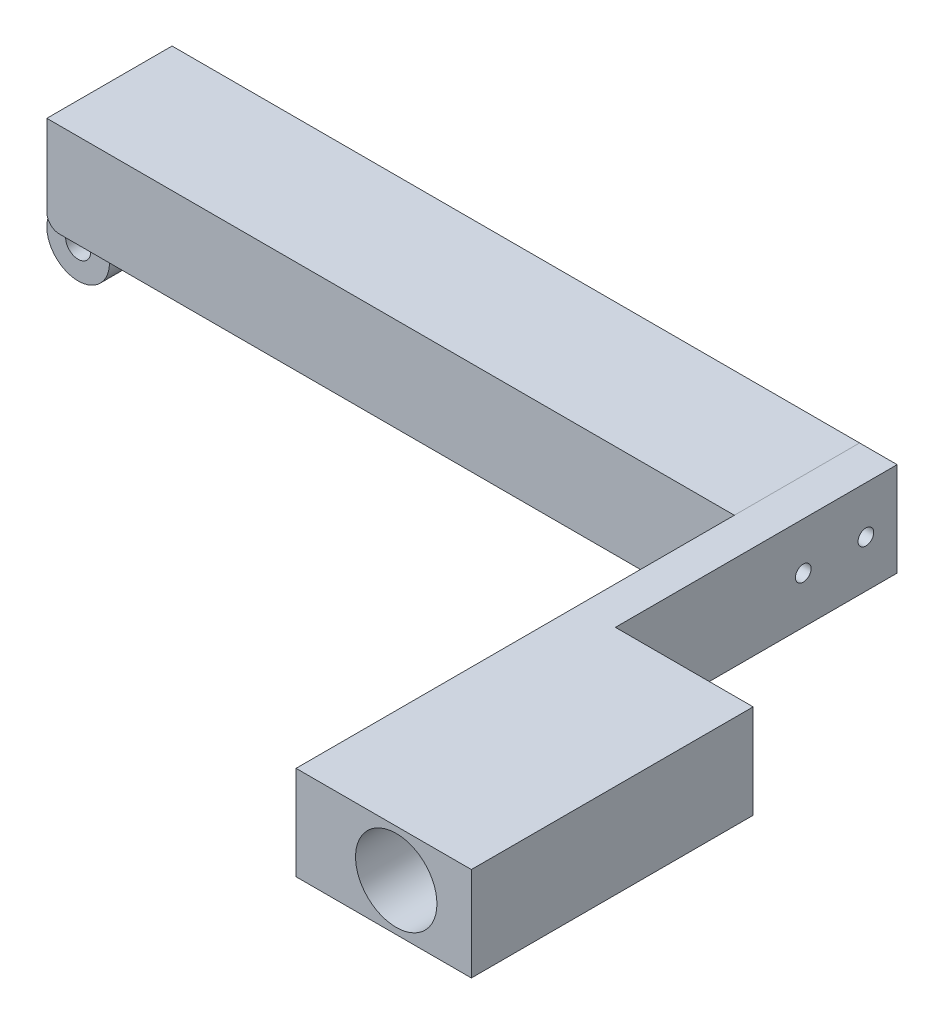
SolidWorks part; units mm, degrees
ref_plane "Front Plane" through (0, 0, 0) normal (0, 0, 1) x (1, 0, 0)
ref_plane "Top Plane" through (0, 0, 0) normal (0, 1, 0) x (1, 0, 0)
ref_plane "Right Plane" through (0, 0, 0) normal (1, 0, 0) x (0, 0, -1)
sketch "Sketch4" plane through (0, 0, 0) normal (1, 0, 0) x (0, 0, -1)
  line L1 (-10, -7.5) -> (10, -7.5)
  line L2 (-10, -7.5) -> (-10, 7.5)
  line L3 (-10, 7.5) -> (10, 7.5)
  line L4 (10, -7.5) -> (10, 7.5)
  line L5 (-10, -7.5) -> (10, 7.5) construction
  line L6 (-10, 7.5) -> (10, -7.5) construction
  point P0 (0, 0)
  dimension "D1" = 20
  dimension "D2" = 15
extrude "Boss-Extrude1" add sketch "Sketch4" along normal blind 115.8
sketch "Sketch5" plane through (0, 0, 10) normal (0, 0, 1) x (1, 0, 0)
  line L0 (115.8, -7.5) -> (0, -7.5) construction
  line L1 (115.8, 7.5) -> (109.8, 7.5)
  line L2 (115.8, 7.5) -> (115.8, -7.5)
  line L3 (115.8, -7.5) -> (109.8, -7.5)
  line L4 (109.8, 7.5) -> (109.8, -7.5)
  dimension "D1" = 6
extrude "Boss-Extrude2" add sketch "Sketch5" along normal blind 35
sketch "Sketch6" plane through (0, 0, 45) normal (0, 0, 1) x (1, 0, 0)
  line L0 (115.8, -7.5) -> (115.8, 7.5) construction
  line L2 (109.8, -7.5) -> (137.8, -7.5)
  line L3 (109.8, -7.5) -> (109.8, 7.5)
  line L4 (109.8, 7.5) -> (137.8, 7.5)
  line L5 (137.8, -7.5) -> (137.8, 7.5)
  line L6 (123.8, 7.5) -> (123.8, -7.5) construction
  line L7 (109.8, 0) -> (137.8, 0) construction
  circle A0 centre (125.8, 0) radius 6.5
  point P6 (115.8, 0)
  point P213 (123.8, 0)
  dimension "D3" = 13
  dimension "D2" = 10
  dimension "D1" = 28
extrude "Boss-Extrude3" add sketch "Sketch6" against normal blind 10 and the other way blind 35
sketch "Sketch7" plane through (0, 0, 0) normal (0, 0, 1) x (1, 0, 0)
  line L0 (5, -12.5) -> (5, -7.5)
  line L1 (109.8, -7.5) -> (0, -7.5) construction
  line L2 (0, 7.5) -> (0, -7.5) construction
  line L3 (0, -7.5) -> (5, -7.5)
  circle A0 centre (0, -12.5) radius 2
  arc A2 (0, -7.5) -> (5, -12.5) centre (0, -12.5) ccw
  circle A3 centre (0, -12.5) radius 5 construction
  arc A4 (0, -7.5) -> (5, -12.5) centre (0, -12.5) cw construction
  dimension "D1" = 4
  dimension "D2" = 3
extrude "Boss-Extrude4" add sketch "Sketch7" along normal mid plane 10
fillet "Fillet1" radius 2 2 edges at (0, -7.5, -7.5) (0, -7.5, 7.5)
fillet "Fillet2" radius 5 1 edges at (5, -7.5, 0)
hole_wizard "M3x0.5 Tapped Hole2" positions "Sketch14" profile "Sketch15" tap size "M3x0.5" standard "ANSI Metric"
sketch "Sketch14" plane through (115.8, 0, 0) normal (1, 0, 0) x (0, 0, -1)
  line L1 (-10, 7.5) -> (10, 7.5)
  line L2 (-10, 7.5) -> (-10, -7.5)
  line L3 (-10, -7.5) -> (10, -7.5)
  line L4 (10, 7.5) -> (10, -7.5)
  line L5 (10, 7.5) -> (-35, 7.5) construction
  line L6 (-5, 0) -> (5, 0) construction
  point P49 (-5, 0)
  point P50 (5, 0)
  point P55 (0, 7.5)
  point P56 (0, 0)
  dimension "D1" = 5
sketch "Sketch15" plane through (115.8, 0, -5) normal (0, 1, 0) x (0, 0, -1)
  line L0 (0, 0) -> (0, 15.7511)
  line L1 (0, 15.7511) -> (1.25, 15)
  line L2 (1.25, 15) -> (1.25, 0)
  line L5 (1.25, 0) -> (0, 0)
  line L10 (0, 15.7511) -> (-1.25, 15) construction
  line L11 (0, -6.35) -> (0, 107.95) construction
  dimension "Tap Drill Dia." = 2.5
  dimension "Tap Drill Depth" = 15
  dimension "Drill Angle" = 118
cosmetic thread "Hole Thread9" parameters "D1"=6, "D2"=3
cosmetic thread "Hole Thread10" parameters "D1"=6, "D2"=3
hole_wizard "CBORE for M3 SHCS2" [suppressed] positions "Sketch16" profile "Sketch17" counterbore size "M3" standard "ANSI Metric"
sketch "Sketch16" plane through (115.8, 0, 0) normal (1, 0, 0) x (0, 0, -1)
  point P0 (-5, 0)
  point P3 (5, 0)
sketch "Sketch17" plane through (115.8, 0, 5) normal (0, 1, 0) x (0, 0, -1)
  line L0 (0, 0) -> (0, 7.0215)
  line L1 (0, 7.0215) -> (1.7, 6)
  line L2 (1.7, 6) -> (1.7, 3)
  line L3 (1.7, 3) -> (3.25, 3)
  line L4 (3.25, 3) -> (3.25, 0)
  line L5 (3.25, 0) -> (0, 0)
  line L10 (0, 7.0215) -> (-1.7, 6) construction
  line L11 (0, -6.35) -> (0, 107.95) construction
  dimension "Hole Dia." = 3.4
  dimension "Hole Depth" = 6
  dimension "C'Bore Dia." = 6.5
  dimension "C'Bore Depth" = 3
  dimension "Drill Angle" = 118
sketch "Sketch8" plane through (0, 7.5, 0) normal (0, 1, 0) x (1, 0, 0)
  line L0 (109.8, -10) -> (109.8, 10)
  line L1 (115.8, 10) -> (0, 10) construction
sketch "Sketch19" plane through (0, 0, 0) normal (-1, 0, 0) x (0, 0, 1)
  line L5 (-10, 7.5) -> (10, 7.5) construction
  line L6 (-10, -5.5) -> (-5, -5.5) construction
  line L7 (10, 7.5) -> (10, -5.5) construction
  line L8 (-10, -5.5) -> (-10, 7.5) construction
  line L9 (-5, -7.5) -> (-10, -7.5) construction
  circle A0 centre (-7.5, 5) radius 1.5
  circle A1 centre (-2.5, 5) radius 1.5
  circle A2 centre (2.5, 5) radius 1.5
  circle A3 centre (7.5, 5) radius 1.5
  circle A4 centre (-2.5, 1) radius 1.5
  circle A5 centre (2.5, 1) radius 1.5
  circle A6 centre (7.5, 1) radius 1.5
  circle A7 centre (-2.5, -3) radius 1.5
  circle A8 centre (2.5, -3) radius 1.5
  circle A9 centre (7.5, -3) radius 1.5
  circle A10 centre (-7.5, 1) radius 1.5
  circle A11 centre (-7.5, -3) radius 1.5
  point P2 (-10.118, 10.9396)
  point P3 (-0.5057, 10.9159)
  point P4 (-7.8145, 5.5619)
  point P30 (-10.4376, 10.6326)
  point P31 (3.217, 10.7735)
  point P32 (3.5069, 10.7735)
  point P35 (-2.8841, 5.7735)
  point P36 (-2.8841, 5.7735)
  dimension "D1" = 3
  dimension "D4" = 2.5
  dimension "D5" = 2.5
  dimension "D6" = 2.5
  dimension "D7" = 2.5
  dimension "D8" = 4.5
  dimension "D2" = 4
  dimension "D3" = 3
extrude "Cut-Extrude3" cut sketch "Sketch19" against normal blind 2.5
split "Split2" trim tools "Sketch8" bodies to split 116 resulting bodies 112 113
